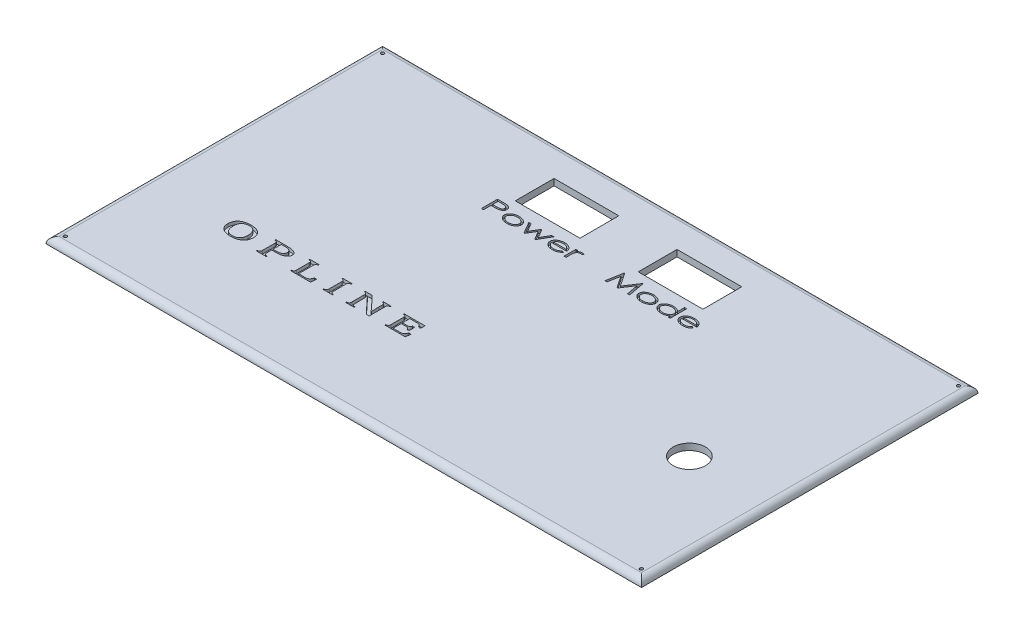
SolidWorks part; units mm, degrees
ref_plane "Front Plane" through (0, 0, 0) normal (0, 0, 1) x (1, 0, 0)
ref_plane "Top Plane" through (0, 0, 0) normal (0, 1, 0) x (1, 0, 0)
ref_plane "Right Plane" through (0, 0, 0) normal (1, 0, 0) x (0, 0, -1)
sketch "Sketch1" plane through (0, 0, 0) normal (0, 1, 0) x (1, 0, 0)
  line L1 (92, -52) -> (-92, -52)
  line L2 (92, -52) -> (92, 52)
  line L3 (92, 52) -> (-92, 52)
  line L4 (-92, -52) -> (-92, 52)
  line L5 (92, -52) -> (-92, 52) construction
  line L6 (92, 52) -> (-92, -52) construction
  line L7 (-29, 42) -> (-9, 42)
  line L8 (-29, 42) -> (-29, 30)
  line L9 (-29, 30) -> (-9, 30)
  line L10 (-9, 42) -> (-9, 30)
  line L11 (9, 42) -> (29, 42)
  line L12 (9, 42) -> (9, 30)
  line L13 (9, 30) -> (29, 30)
  line L14 (29, 42) -> (29, 30)
  circle A0 centre (66.2671, -11.4513) radius 5
  point P0 (0, 0)
  point P10 (-29, 36)
  point P15 (19, 42)
  point P16 (29, 36)
  dimension "D1" = 104
  dimension "D2" = 184
  dimension "D3" = 12
  dimension "D4" = 20
  dimension "D5" = 63
  dimension "D6" = 10
  dimension "D7" = 20
  dimension "D8" = 12
  dimension "D9" = 10
  dimension "D10" = 63
extrude "Boss-Extrude1" add sketch "Sketch1" along normal blind 2
sketch "Sketch2" plane through (0, 2, 0) normal (0, 1, 0) x (1, 0, 0)
  line L0 (-89, 52) -> (-89, -52)
  line L1 (92, 52) -> (-92, 52) construction
  line L2 (-92, -52) -> (92, -52) construction
  line L3 (-92, 49) -> (92, 49)
  line L4 (-92, 52) -> (-92, -52) construction
  line L5 (92, -52) -> (92, 52) construction
  line L6 (89, 52) -> (89, -52)
  line L7 (-92, -49) -> (92, -49)
  circle A0 centre (-89, 49) radius 0.5
  circle A1 centre (-89, -49) radius 0.5
  circle A2 centre (89, 49) radius 0.5
  circle A3 centre (89, -49) radius 0.5
  dimension "D1" = 3
  dimension "D2" = 3
  dimension "D3" = 3
  dimension "D4" = 3
extrude "Cut-Extrude1" cut sketch "Sketch2" against normal up to surface (2 mm away) contours L3 A0 L0 | L0 A0 L3 | L3 A0 L0 | L0 A0 L3 | L0 A1 L7 | L7 A1 L0 | L0 A1 L7 | L7 A1 L0 | L6 A3 L7 | L7 A3 L6 | L6 A3 L7 | L7 A3 L6 | L3 A2 L6 | L6 A2 L3 | L3 A2 L6 | L6 A2 L3 region at (-88.7878, 2, -49.2122) region at (-89.2122, 2, -49.2122) region at (-88.7878, 2, -48.7878) region at (-89.2122, 2, -48.7878) region at (88.7878, 2, -49.2122) region at (88.7878, 2, -48.7878) region at (-88.7878, 2, 48.7878) region at (-89.2122, 2, 48.7878) region at (89.2122, 2, -49.2122) region at (89.2122, 2, -48.7878) region at (-88.7878, 2, 49.2122) region at (-89.2122, 2, 49.2122) region at (89.2122, 2, 48.7878) region at (88.7878, 2, 48.7878) region at (88.7878, 2, 49.2122) region at (89.2122, 2, 49.2122) up to face at (-19, 0, -36)
fillet "Fillet3" radius 2 4 edges at (92, 2, 0) (0, 2, 52) (0, 2, -52) (-92, 2, 0)
sketch "Sketch3" plane through (0, 2, 0) normal (0, 1, 0) x (1, 0, 0)
  text T0 "Power"
  text T1 "Mode"
  text T2 "OPLINE" font "Cambria" height 6
extrude "Cut-Extrude2" cut sketch "Sketch3" against normal blind 1
sketch "Sketch5" plane through (0, 2, 0) normal (0, 1, 0) x (1, 0, 0)
  text T0 "Power"
extrude "Boss-Extrude2" add sketch "Sketch5" against normal through all
sketch "Sketch6" plane through (0, 2, 0) normal (0, 1, 0) x (1, 0, 0)
  line L1 (-30.5368, 27.4523) -> (29.9199, 27.4523)
  line L2 (-30.5368, 27.4523) -> (-30.5368, 18.61)
  line L3 (-30.5368, 18.61) -> (29.9199, 18.61)
  line L4 (29.9199, 27.4523) -> (29.9199, 18.61)
extrude "Boss-Extrude3" add sketch "Sketch6" against normal through all
sketch "Sketch7" plane through (0, 2, 0) normal (0, 1, 0) x (1, 0, 0)
  text T0 "Power" font "Century Gothic" height 5
extrude "Cut-Extrude3" cut sketch "Sketch7" against normal blind 1
sketch "Sketch8" plane through (0, 2, 0) normal (0, 1, 0) x (1, 0, 0)
  text T0 "Mode" font "Century Gothic" height 5
extrude "Cut-Extrude4" cut sketch "Sketch8" against normal blind 1
